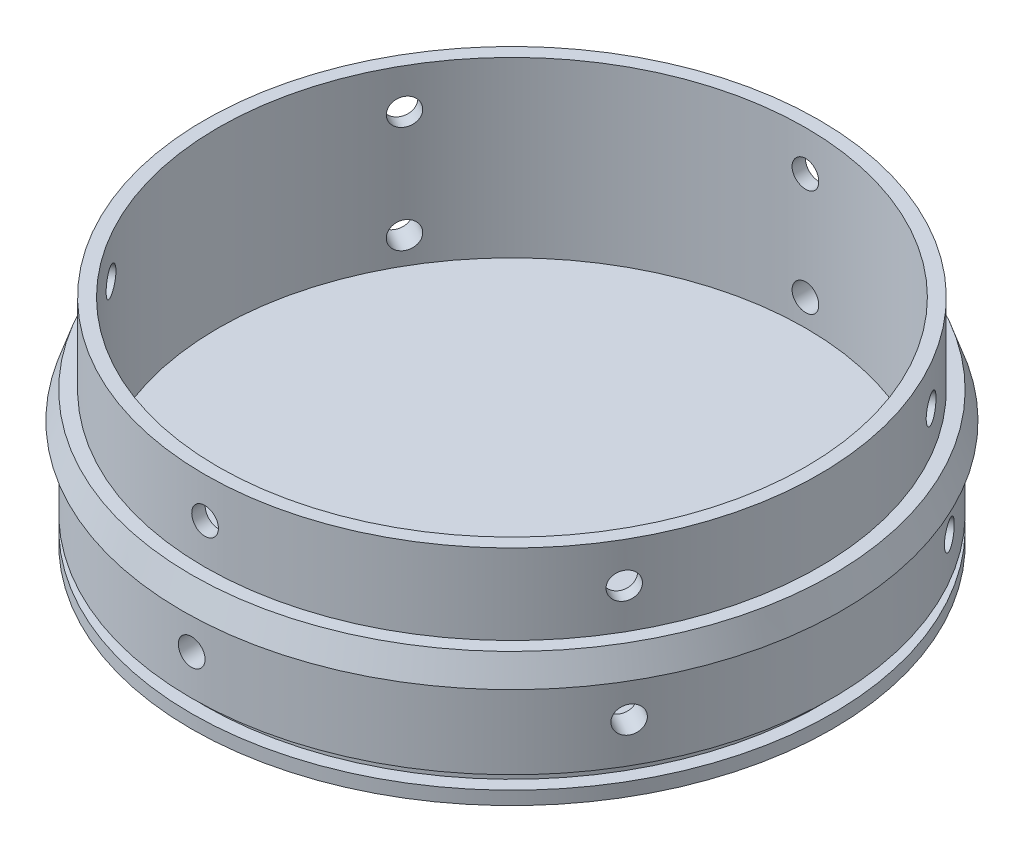
SolidWorks part; units mm, degrees
material "2024-T4"
ref_plane "Front Plane" through (0, 0, 0) normal (0, 0, 1) x (1, 0, 0)
ref_plane "Top Plane" through (0, 0, 0) normal (0, 1, 0) x (1, 0, 0)
ref_plane "Right Plane" through (0, 0, 0) normal (1, 0, 0) x (0, 0, -1)
sketch "Sketch1" plane through (0, 0, 0) normal (0, 1, 0) x (1, 0, 0)
  circle A0 centre (0, 0) radius 78.359
  circle A2 centre (0, 0) radius 76.2
  circle A3 centre (0, 0) radius 73.025
  dimension "D1" = 156.718
  dimension "D2" = 152.4
  dimension "D3" = 3.175
extrude "Boss-Extrude1" add sketch "Sketch1" along normal blind 6.35 contours A0 A2 region at (-78.1374, 0, 0)
extrude "Boss-Extrude2" add sketch "Sketch1<3>" along normal blind 25.4 contours A2 A3 region at (-74.0447, 0, 0)
sketch "Sketch1<3>" plane through (0, 0, 0) normal (0, 1, 0) x (1, 0, 0) same geometry as "Sketch1"
sketch "Sketch2" plane through (0, 0, 0) normal (0, -1, 0) x (1, 0, 0)
  circle A0 centre (0, 0) radius 73.025 construction
  circle A1 centre (0, 0) radius 73.025
  circle A2 centre (0, 0) radius 76.2
  dimension "D1" = 3.175
extrude "Boss-Extrude3" add sketch "Sketch2" along normal blind 25.4
sketch "Sketch3" plane through (0, -25.4, 0) normal (0, -1, 0) x (1, 0, 0)
  circle A1 centre (0, 0) radius 76.2
  circle A2 centre (0, 0) radius 76.2
  dimension "D1" = 0
extrude "Boss-Extrude4" add sketch "Sketch3" against normal blind 9.525
sketch "Sketch5" plane through (0, 0, 0) normal (0, 0, 1) x (1, 0, 0)
  line L0 (-76.2, -25.4) -> (76.2, -25.4) construction
  line L1 (-76.2, 0) -> (-76.2, -25.4) construction
  line L2 (-76.2, -25.4) -> (76.2, -25.4)
  line L3 (-76.2, 0) -> (-76.2, -25.4)
  line L4 (-76.2, -22.225) -> (-73.025, -22.225)
  line L5 (-73.025, -22.225) -> (-73.025, -19.05)
  line L6 (-73.025, -19.05) -> (-76.2, -19.05)
  line L7 (0, 0) -> (0, -25.4) construction
  dimension "D1" = 3.175
  dimension "D2" = 3.175
  dimension "D3" = 3.175
revolve "Cut-Revolve1" cut sketch "Sketch5" angle 360 about L7 region at (-74.6125, -20.6375, 0)
ref_plane "Plane1" through (0, 0, 76.2) normal (0, 0, 1) x (1, 0, 0)
chamfer "Chamfer1" distance 6.35 distance2 2.159 1 edges at (0, 6.35, 78.359) first distance on face at (0, 6.35, 78.359)
sketch "Sketch6" plane through (0, 25.4, 0) normal (0, 1, 0) x (1, 0, 0)
  circle A1 centre (0, 0) radius 76.2
  circle A2 centre (0, 0) radius 76.2
  dimension "D1" = 0
extrude "Cut-Extrude1" cut sketch "Sketch6" against normal blind 19.05
sketch "Sketch7" plane through (0, -15.875, 0) normal (0, 1, 0) x (1, 0, 0)
  circle A0 centre (0, 0) radius 69.85
  circle A1 centre (0, 0) radius 73.025
  dimension "D1" = 146.05
  dimension "D2" = 139.7
extrude "Boss-Extrude5" add sketch "Sketch7" along normal blind 41.275
sketch "Sketch8" plane through (0, 0, 76.2) normal (0, 0, 1) x (1, 0, 0)
  line L0 (76.2, 6.35) -> (-76.2, 6.35) construction
  line L1 (76.2, 6.35) -> (-76.2, 6.35)
  circle A0 centre (0, -9.525) radius 3.175
  circle A1 centre (0, 15.875) radius 3.175
  dimension "D1" = 6.35
  dimension "D2" = 6.35
  dimension "D3" = 9.525
  dimension "D4" = 9.525
extrude "Cut-Extrude2" cut sketch "Sketch8" against normal up to next contours A1 | A0 region at (0, -9.525, 76.2) region at (0, 15.875, 76.2)
pattern_circular "CirPattern1" count 6 over 360 about axis through (0, 25.4, 0) along (0, -1, 0) of "Cut-Extrude2" reverse direction yes
